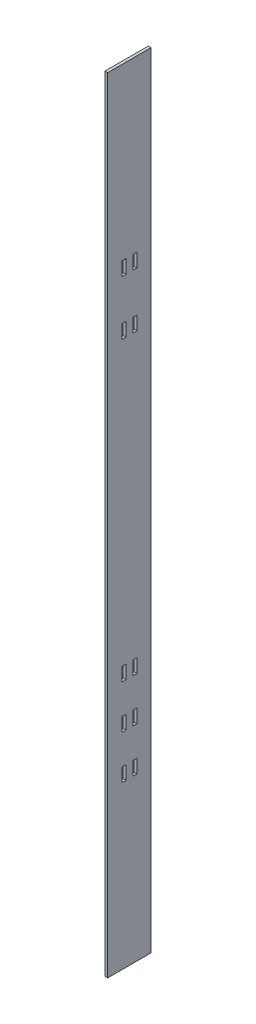
SolidWorks part; units mm, degrees
ref_plane "Front Plane" through (0, 0, 0) normal (0, 0, 1) x (1, 0, 0)
ref_plane "Top Plane" through (0, 0, 0) normal (0, 1, 0) x (1, 0, 0)
ref_plane "Right Plane" through (0, 0, 0) normal (1, 0, 0) x (0, 0, -1)
sketch "Sketch1" plane through (0, 0, 0) normal (1, 0, 0) x (0, 0, -1)
  line L1 (-25.4, 457.2) -> (25.4, 457.2)
  line L2 (-25.4, 457.2) -> (-25.4, -457.2)
  line L3 (-25.4, -457.2) -> (25.4, -457.2)
  line L4 (25.4, 457.2) -> (25.4, -457.2)
  line L5 (-25.4, 457.2) -> (25.4, -457.2) construction
  line L6 (-25.4, -457.2) -> (25.4, 457.2) construction
  point P0 (0, 0)
  dimension "D1" = 914.4
  dimension "D2" = 50.8
extrude "Boss-Extrude1" add sketch "Sketch1" along normal blind 3.175
sketch "Sketch2" plane through (3.175, 0, 0) normal (1, 0, 0) x (0, 0, -1)
  line L0 (-25.4, -457.2) -> (25.4, -457.2) construction
  line L1 (4, -201.6125) -> (8.7625, -201.6125)
  line L2 (4, -201.6125) -> (4, -217.4875)
  line L3 (4, -217.4875) -> (8.7625, -217.4875)
  line L4 (8.7625, -201.6125) -> (8.7625, -217.4875)
  line L5 (4, -201.6125) -> (8.7625, -217.4875) construction
  line L6 (4, -217.4875) -> (8.7625, -201.6125) construction
  point P0 (6.3813, -209.55)
  dimension "D1" = 4.7625
  dimension "D2" = 15.875
  dimension "D3" = 239.7125
  dimension "D4" = 4
extrude "Cut-Extrude1" cut sketch "Sketch2" against normal through all
mirror "Mirror1" about plane through (0, 0, 0) normal (0, 0, 1) of "Cut-Extrude1"
pattern_linear "LPattern1" count 2 spacing 50.8 along (0, 1, 0) count 2 spacing 50.8 along (0, -1, 0) of "Mirror1"
sketch "Sketch3" plane through (3.175, 0, 0) normal (1, 0, 0) x (0, 0, -1)
  line L0 (8.7625, -150.8125) -> (4, -150.8125) construction
  line L1 (4, 195.2625) -> (8.7625, 195.2625)
  line L2 (4, 195.2625) -> (4, 179.3875)
  line L3 (4, 179.3875) -> (8.7625, 179.3875)
  line L4 (8.7625, 195.2625) -> (8.7625, 179.3875)
  line L5 (4, 195.2625) -> (8.7625, 179.3875) construction
  line L6 (4, 179.3875) -> (8.7625, 195.2625) construction
  line L7 (8.7625, -166.6875) -> (8.7625, -150.8125) construction
  line L8 (4, -150.8125) -> (4, -166.6875) construction
  line L9 (0, 0) -> (0, 53.0447) construction
  line L10 (-4, 179.3875) -> (-8.7625, 195.2625) construction
  line L11 (-4, 195.2625) -> (-8.7625, 179.3875) construction
  line L12 (-8.7625, 195.2625) -> (-8.7625, 179.3875)
  line L13 (-4, 179.3875) -> (-8.7625, 179.3875)
  line L14 (-4, 195.2625) -> (-4, 179.3875)
  line L15 (-4, 195.2625) -> (-8.7625, 195.2625)
  point P0 (6.3812, 187.325)
  point P12 (6.3812, 179.3875)
  point P19 (-6.3812, 187.325)
  dimension "D1" = 330.2
extrude "Cut-Extrude2" cut sketch "Sketch3" against normal through all
pattern_linear "LPattern2" count 2 spacing 63.5 along (0, 1, 0) of "Cut-Extrude2"
